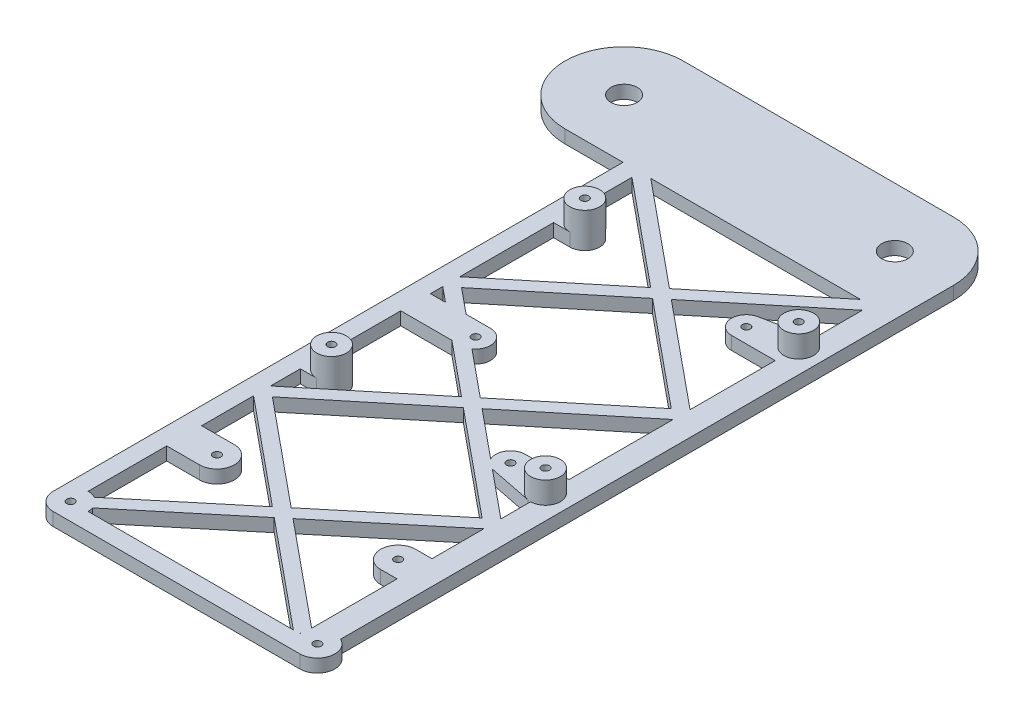
SolidWorks part; units mm, degrees
ref_plane "Front Plane" through (0, 0, 0) normal (0, 0, 1) x (1, 0, 0)
ref_plane "Top Plane" through (0, 0, 0) normal (0, 1, 0) x (1, 0, 0)
ref_plane "Right Plane" through (0, 0, 0) normal (1, 0, 0) x (0, 0, -1)
ref_plane "SHIFTER SCREW HOLE MOUNT PLANE" through (0, -50.5, 0) normal (0, 1, 0) x (1, 0, 0)
sketch "SHIFTER SCREW HOLE LOCATIONS" plane through (0, -50.5, 0) normal (0, 1, 0) x (1, 0, 0)
  point P0 (12, 93)
  point P1 (-50, 93)
sketch "Sketch2" plane through (0, -50.5, 0) normal (0, 1, 0) x (1, 0, 0)
  line L0 (-50, 93) -> (12, 93) construction
  line L1 (-50, 106.5) -> (12, 106.5)
  line L2 (-50, 79.5) -> (12, 79.5)
  arc A0 (-50, 106.5) -> (-50, 79.5) centre (-50, 93) ccw
  arc A1 (12, 79.5) -> (12, 106.5) centre (12, 93) ccw
  circle A2 centre (-50, 93) radius 3
  circle A3 centre (12, 93) radius 3
  point P4 (-19, 93)
  dimension "D1" = 13.5
  dimension "D2" = 6
extrude "SHIFTER HOLE IF" add sketch "Sketch2" against normal blind 3
sketch "Sketch3" plane through (0, -50.5, 0) normal (0, 1, 0) x (1, 0, 0)
  line L1 (-29, 63) -> (20, 63) construction
  line L2 (-29, 63) -> (-29, 5) construction
  line L3 (-29, 5) -> (20, 5) construction
  line L4 (20, 63) -> (20, 5) construction
  circle A0 centre (-29, 63) radius 0.9
  circle A1 centre (20, 63) radius 0.9
  circle A2 centre (20, 5) radius 0.9
  circle A3 centre (-29, 5) radius 0.9
  circle A4 centre (-29, 63) radius 3.4
  circle A5 centre (20, 63) radius 3.4
  circle A6 centre (20, 5) radius 3.4
  circle A7 centre (-29, 5) radius 3.4
  dimension "D1" = 1.8
  dimension "D2" = 49
  dimension "D3" = 58
  dimension "D5" = 20
  dimension "D6" = 5
  dimension "D4" = 2.5
extrude "RPI4 SCREW BOSSES" add sketch "Sketch3" along normal blind 5 and the other way blind 3 separate body
sketch "Sketch4" plane through (0, -50.5, 0) normal (0, 1, 0) x (1, 0, 0)
  line L0 (10, 61) -> (10, 7) construction
  line L1 (20, 63) -> (20, 5) construction
  line L2 (20, 34) -> (10, 34) construction
  circle A0 centre (10, 61) radius 0.9
  circle A1 centre (10, 7) radius 0.9
  circle A2 centre (10, 61) radius 3.4
  circle A3 centre (10, 7) radius 3.4
  circle A4 centre (-19, 28) radius 0.9
  circle A5 centre (-19, 28) radius 3.4
  dimension "D2" = 1.8
  dimension "D3" = 6.8
  dimension "D1" = 54
  dimension "D4" = 29
  dimension "D5" = 21
  dimension "D6" = 10
extrude "CAN SWITCH SCREW BOSSES" add sketch "Sketch4" against normal blind 3 separate body
sketch "Sketch5" plane through (0, -50.5, 0) normal (0, 1, 0) x (1, 0, 0)
  line L0 (-25.25, -25) -> (16.25, -25) construction
  line L1 (-32.75, -51) -> (23.75, -51) construction
  line L2 (-4.5, -51) -> (-4.5, -25) construction
  line L3 (-29, 5) -> (20, 5) construction
  line L4 (-4.5, -25) -> (-4.5, 5) construction
  circle A0 centre (-25.25, -25) radius 0.9
  circle A1 centre (-32.75, -51) radius 0.9
  circle A2 centre (16.25, -25) radius 0.9
  circle A3 centre (23.75, -51) radius 0.9
  circle A4 centre (-32.75, -51) radius 4
  circle A5 centre (-25.25, -25) radius 4
  circle A6 centre (16.25, -25) radius 4
  circle A7 centre (23.75, -51) radius 4
  dimension "D4" = 1.8
  dimension "D6" = 30
  dimension "D5" = 8
  dimension "D1" = 41.5
  dimension "D2" = 26
  dimension "D3" = 56.5
extrude "5V REG MOUNT POSTS" add sketch "Sketch5" against normal blind 3 separate body
sketch "Sketch6" plane through (0, -50.5, 0) normal (0, 1, 0) x (1, 0, 0)
  line L0 (25.5, 93) -> (25.5, -47.4031)
  line L1 (-36.75, 79.5) -> (-36.75, -51)
  line L2 (-50, 79.5) -> (12, 79.5) construction
  line L3 (-36.75, 79.5) -> (12, 79.5)
  line L4 (-32.75, -55) -> (23.75, -55)
  arc A0 (12, 79.5) -> (12, 106.5) centre (12, 93) ccw construction
  circle A1 centre (23.75, -51) radius 4 construction
  arc A2 (23.75, -55) -> (25.5, -47.4031) centre (23.75, -51) ccw
  circle A3 centre (-32.75, -51) radius 4 construction
  arc A4 (12, 79.5) -> (25.5, 93) centre (12, 93) ccw
  arc A5 (-36.75, -51) -> (-32.75, -55) centre (-32.75, -51) ccw
  circle A6 centre (-25.25, -25) radius 0.9 construction
  circle A7 centre (16.25, -25) radius 0.9 construction
  circle A8 centre (23.75, -51) radius 0.9 construction
  circle A9 centre (-32.75, -51) radius 0.9 construction
  circle A10 centre (-25.25, -25) radius 0.9
  circle A11 centre (16.25, -25) radius 0.9
  circle A12 centre (23.75, -51) radius 0.9
  circle A13 centre (-32.75, -51) radius 0.9
  circle A14 centre (-29, 63) radius 0.9 construction
  circle A15 centre (20, 63) radius 0.9 construction
  circle A16 centre (10, 61) radius 0.9 construction
  circle A17 centre (-19, 28) radius 0.9 construction
  circle A18 centre (10, 7) radius 0.9 construction
  circle A19 centre (20, 5) radius 0.9 construction
  circle A20 centre (-29, 5) radius 0.9 construction
  circle A21 centre (-29, 63) radius 0.9
  circle A22 centre (20, 63) radius 0.9
  circle A23 centre (10, 61) radius 0.9
  circle A24 centre (-19, 28) radius 0.9
  circle A25 centre (10, 7) radius 0.9
  circle A26 centre (20, 5) radius 0.9
  circle A27 centre (-29, 5) radius 0.9
extrude "IF LINK" add sketch "Sketch6" against normal blind 3
sketch "Sketch7" plane through (0, -50.5, 0) normal (0, 1, 0) x (1, 0, 0)
  line L0 (-32.75, 66.4) -> (-32.75, 79.5)
  line L1 (-36.75, 79.5) -> (12, 79.5) construction
  line L2 (-32.75, 79.5) -> (20, 79.5)
  line L3 (20, 79.5) -> (20, 66.4)
  line L4 (19.3332, 66.334) -> (9.3332, 64.334)
  line L5 (10, 57.6) -> (20, 57.6)
  line L6 (20, 57.6) -> (20, 10.4)
  line L7 (20, 10.4) -> (10, 10.4)
  line L8 (10, 61) -> (10, 7) construction
  line L9 (9.3332, 3.666) -> (19.3332, 1.666)
  line L10 (20, 1.6) -> (20, -21)
  line L11 (20, -21) -> (16.25, -21)
  line L12 (16.25, -29) -> (20, -29)
  line L13 (20, -29) -> (20, -49.6081)
  line L14 (19.75, -51) -> (-28.75, -51)
  line L15 (-32.75, -47) -> (-32.75, -29)
  line L16 (-32.75, -29) -> (-25.25, -29)
  line L17 (-25.25, -21) -> (-32.75, -21)
  line L18 (-32.75, -21) -> (-32.75, 1.6)
  line L19 (-32.75, 1.6) -> (-29, 1.6)
  line L20 (-29, 8.4) -> (-32.75, 8.4)
  line L21 (-32.75, 8.4) -> (-32.75, 24.6)
  line L22 (-32.75, 24.6) -> (-19, 24.6)
  line L23 (-19, 31.4) -> (-32.75, 31.4)
  line L24 (-32.75, 31.4) -> (-32.75, 59.6)
  line L25 (-32.75, 59.6) -> (-29, 59.6)
  line L26 (-32.75, 66.4) -> (-29, 66.4)
  circle A0 centre (-29, 63) radius 3.4 construction
  circle A1 centre (20, 63) radius 3.4 construction
  arc A2 (20, 66.4) -> (19.3332, 66.334) centre (20, 63) ccw
  circle A3 centre (10, 61) radius 3.4 construction
  arc A4 (9.3332, 64.334) -> (10, 57.6) centre (10, 61) ccw
  circle A5 centre (10, 7) radius 3.4 construction
  arc A6 (10, 10.4) -> (9.3332, 3.666) centre (10, 7) ccw
  circle A7 centre (20, 5) radius 3.4 construction
  arc A8 (19.3332, 1.666) -> (20, 1.6) centre (20, 5) ccw
  circle A9 centre (16.25, -25) radius 4 construction
  arc A10 (16.25, -21) -> (16.25, -29) centre (16.25, -25) ccw
  circle A11 centre (23.75, -51) radius 4 construction
  arc A12 (20, -49.6081) -> (19.75, -51) centre (23.75, -51) ccw
  circle A13 centre (-32.75, -51) radius 4 construction
  arc A14 (-28.75, -51) -> (-32.75, -47) centre (-32.75, -51) ccw
  circle A15 centre (-19, 28) radius 3.4 construction
  circle A16 centre (-25.25, -25) radius 4 construction
  circle A17 centre (-29, 5) radius 3.4 construction
  arc A18 (-29, 59.6) -> (-29, 66.4) centre (-29, 63) ccw
  arc A19 (-19, 24.6) -> (-19, 31.4) centre (-19, 28) ccw
  arc A20 (-25.25, -29) -> (-25.25, -21) centre (-25.25, -25) ccw
  arc A21 (-29, 1.6) -> (-29, 8.4) centre (-29, 5) ccw
extrude "WEIGHT RELIEF" cut sketch "Sketch7" against normal through all both and the other way through all
sketch "Sketch8" plane through (0, -50.5, 0) normal (0, 1, 0) x (1, 0, 0)
  line L0 (-32.75, 79.5) -> (20, 36.1667)
  line L1 (20, 63) -> (20, 5) construction
  line L2 (20, 79.5) -> (-32.75, 36.1667)
  line L3 (-32.75, 24.6) -> (-32.75, 8.4) construction
  line L4 (-32.75, 59.6) -> (-32.75, 31.4) construction
  line L5 (-32.75, 36.1667) -> (20, -7.1667)
  line L7 (20, -21) -> (20, 1.6) construction
  line L8 (20, 36.1667) -> (-32.75, -7.1667)
  line L9 (-32.75, 1.6) -> (-32.75, -21) construction
  line L10 (-32.75, -7.1667) -> (20, -50.5)
  line L11 (20, -7.1667) -> (-32.0578, -50.4248)
  line L12 (20, -49.6081) -> (20, -29) construction
  circle A8 centre (-32.75, -51) radius 0.9 construction
  dimension "D1" = 43.3333
extrude "RIBBING" add sketch "Sketch8" against normal blind 3 thin thin type mid plane wall 3
